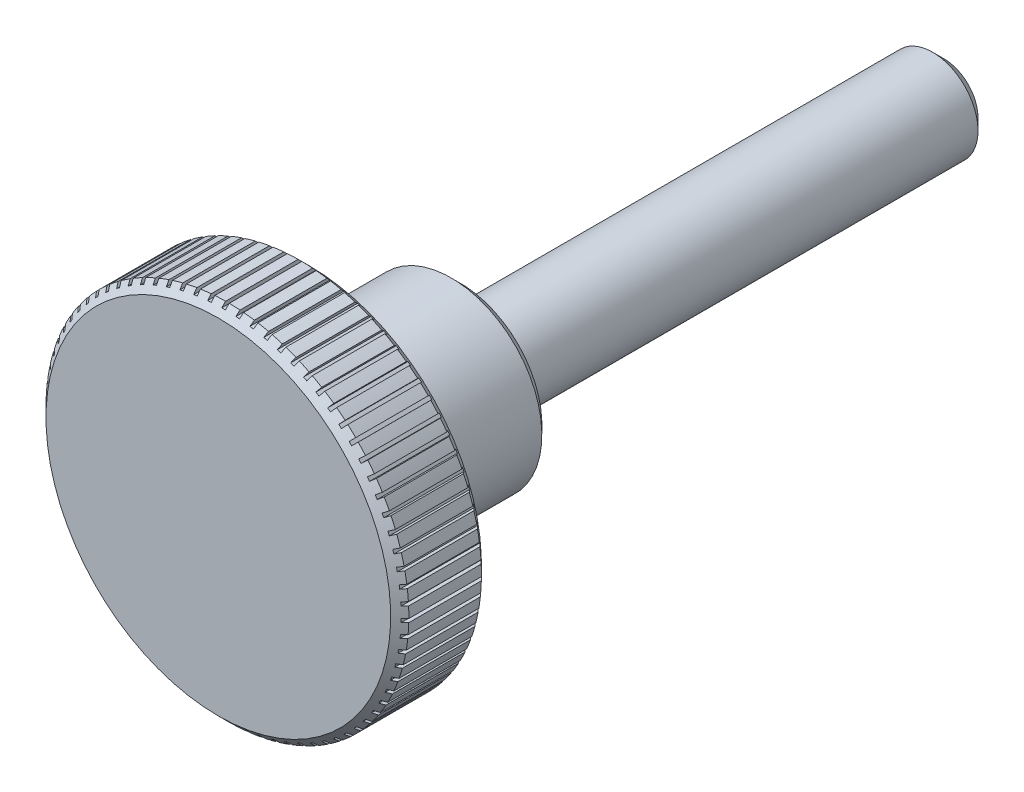
SolidWorks part; units mm, degrees
ref_plane "Front Plane" through (0, 0, 0) normal (0, 0, 1) x (1, 0, 0)
ref_plane "Top Plane" through (0, 0, 0) normal (0, 1, 0) x (1, 0, 0)
ref_plane "Right Plane" through (0, 0, 0) normal (1, 0, 0) x (0, 0, -1)
sketch "Sketch1" plane through (0, 0, 0) normal (1, 0, 0) x (0, 0, -1)
  line L0 (0, 0) -> (16, 0) construction
  line L1 (16, 1.5) -> (16, -1.5) construction
  line L2 (0, 3) -> (0, -3) construction
  line L3 (0, 0) -> (-5, 0) construction
  line L4 (-5, 6) -> (-5, -6) construction
  line L5 (-5, 0) -> (-8, 0) construction
  line L6 (-8, 6) -> (-8, -6) construction
  line L7 (15.9687, 1.5541) -> (16.4687, 1.5541) construction
  line L8 (16.4687, 1.5541) -> (16.2188, 1.1211) construction
  line L9 (16.2188, 1.1211) -> (15.9687, 1.5541) construction
  line L10 (15.9844, 1.5271) -> (16.4531, 1.5271) construction
  line L11 (16, 1.5) -> (16.4375, 1.5) construction
  line L12 (16.1875, 1.1752) -> (16.25, 1.1752) construction
  line L13 (16.2188, 1.1752) -> (16.2188, 1.1211) construction
  line L14 (16.2187, 1.5) -> (16.2187, 1.5541) construction
  point P6 (16, 0)
  point P8 (0, 0)
  point P12 (-5, 0)
  point P17 (-8, 0)
  point P22 (14.25, -1.5)
  point P29 (16.2187, 1.5271)
  dimension "Thread Size" = 3
  dimension "Collar Diameter" = 6
  dimension "Collar Height" = 5
  dimension "Length" = 16
  dimension "Head Diameter" = 12
  dimension "Head Height" = 3
  dimension "D1" = 60
  dimension "Thread Pitch" = 0.5
  dimension "D2" = 0.0625
  dimension "D3" = 1.75
sketch "Sketch2" plane through (0, 0, 0) normal (1, 0, 0) x (0, 0, -1)
  line L0 (-8, 0) -> (-8, 6)
  line L1 (-8, 6) -> (-5, 6)
  line L2 (-5, 6) -> (-5, 3)
  line L3 (-5, 6) -> (-5, -6) construction
  line L4 (-5, 3) -> (0, 3)
  line L5 (16, 0) -> (16, 1.5)
  line L6 (16, 1.5) -> (0, 1.5)
  line L7 (0, 3) -> (0, -3) construction
  line L8 (0, 1.5) -> (0, 3)
  line L9 (-8, 0) -> (16, 0)
revolve "Revolve1" add sketch "Sketch2" angle 360 about L9
chamfer "Chamfer1" distance 0.3 angle 45 3 edges at (0, -3, 0) (0, -6, 5) (0, -6, 8)
chamfer "Chamfer2" distance 0.375 angle 45 1 edges at (0, -1.5, -16)
fillet "Fillet1" radius 0.3 1 edges at (0, -3, 5)
sketch "Ref" plane through (0, 0, 8) normal (0, 0, 1) x (1, 0, 0)
  circle A0 centre (0, 0) radius 6 construction
split "Split1" [suppressed] bodies to split 104
sketch "Sketch3" [suppressed] plane through (0, 0, -16) normal (0, 0, -1) x (-1, 0, 0)
  circle A0 centre (0, 0) radius 1.5
curve "Helix/Spiral1" [suppressed] pitch 0.5 height 16.5 turns 33
sketch "Sketch4" [suppressed] plane through (0, 0, 0) normal (1, 0, 0) x (0, 0, -1)
  line L0 (15.9844, 1.5271) -> (16.4531, 1.5271)
  line L1 (16.4531, 1.5271) -> (16.25, 1.1752)
  line L2 (16.25, 1.1752) -> (16.1875, 1.1752)
  line L3 (16.1875, 1.1752) -> (15.9844, 1.5271)
sweep "Cut-Sweep1" [suppressed] cut profiles "Sketch4" path "Helix/Spiral1"
sketch "Sketch5" [suppressed] plane through (0, 0, 0) normal (0, 0, -1) x (-1, 0, 0)
  circle A0 centre (0, 0) radius 1.5
extrude "Boss-Extrude1" [suppressed] add sketch "Sketch5" along normal through all draft 25 and the other way blind 0.25
ref_plane "Plane1" through (0, 6, 0) normal (0, 1, 0) x (-1, 0, 0)
sketch "Sketch6" plane through (0, 6, 0) normal (0, 1, 0) x (-1, 0, 0)
  line L6 (-0.06, 8) -> (0.06, 8)
  line L8 (-0.06, 8) -> (-0.06, 5)
  line L9 (-0.06, 5) -> (0.06, 5)
  line L10 (0.06, 8) -> (0.06, 5)
  line L11 (-0.06, 8) -> (0.06, 5) construction
  line L12 (-0.06, 5) -> (0.06, 8) construction
  point P4 (0, 6.5)
  point P5 (0, 8)
  point P6 (0, 5)
  dimension "D1" = 0.12
extrude "Cut-Extrude1" cut sketch "Sketch6" against normal blind 0.127
pattern_circular "CirPattern1" count 79 over 360 about axis through (0, 0, 5) along (0, 0, 1) of "Cut-Extrude1"
equation "\"D2@Sketch1\" = \"Thread Pitch@Sketch1\" / 8"
equation "\"D3@Sketch1\" = \"Thread Pitch@Sketch1\" * 3.5"
equation "\"D1@Chamfer1\"=\"Head Height@Sketch1\"/10"
equation "\"D1@Chamfer2\" = \"Thread Pitch@Sketch1\" * .75"
equation "\"D1@Fillet1\"=\"D1@Chamfer1\""
equation "\"D4@Helix/Spiral1\" = \"Thread Pitch@Sketch1\""
equation "\"D3@Helix/Spiral1\" = \"Length@Sketch1\" + \"Thread Pitch@Sketch1\""
equation "\"D2@Boss-Extrude1\" = \"Thread Pitch@Sketch1\" * .5"
equation "\"D1@Sketch6\"=\"Head Diameter@Sketch1\"*0.01"
equation "\"D1@CirPattern1\"=\"Head Diameter@Sketch1\" * 3.14 / \"D1@Sketch6\" * 0.25"
